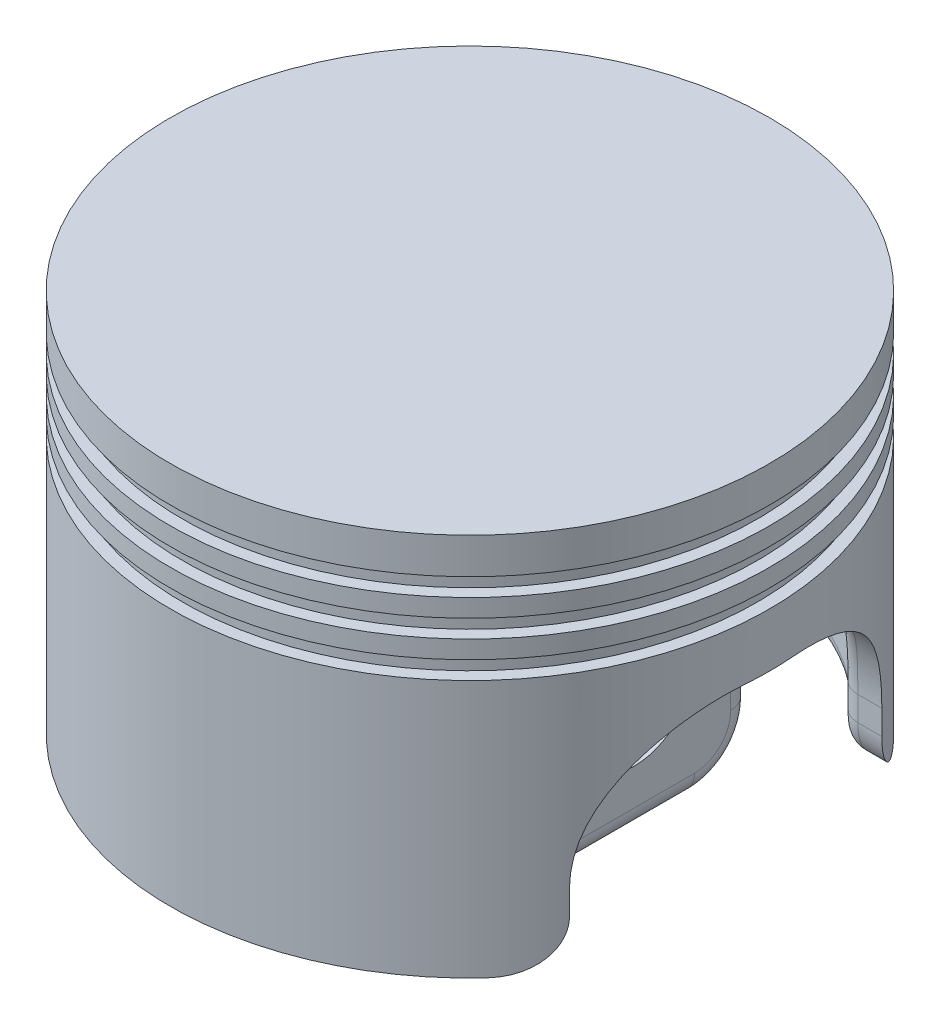
SolidWorks part; units mm, degrees
ref_plane "Front Plane" through (0, 0, 0) normal (0, 0, 1) x (1, 0, 0)
ref_plane "Top Plane" through (0, 0, 0) normal (0, 1, 0) x (1, 0, 0)
ref_plane "Right Plane" through (0, 0, 0) normal (1, 0, 0) x (0, 0, -1)
sketch "Sketch1" plane through (0, 0, 0) normal (1, 0, 0) x (0, 0, -1)
  line L0 (0, 0) -> (63.5, 0)
  line L1 (63.5, 0) -> (63.5, -81.28)
  line L2 (63.5, -81.28) -> (57.15, -81.28)
  line L3 (57.15, -81.28) -> (57.15, -19)
  line L4 (57.15, -19) -> (0, -19)
  line L5 (0, -19) -> (0, 0)
  dimension "D1" = 63.5
  dimension "D2" = 81.28
  dimension "D3" = 6.35
  dimension "D4" = 19
revolve "Revolve1" add sketch "Sketch1" angle 360 about L5
sketch "Sketch2" plane through (0, 0, 0) normal (0, 0, 1) x (1, 0, 0)
  line L0 (63.5, -7.62) -> (60.96, -7.62)
  line L1 (60.96, -7.62) -> (60.96, -11.43)
  line L2 (60.96, -11.43) -> (63.5, -11.43)
  line L3 (63.5, -11.43) -> (63.5, -7.62)
  line L4 (63.5, 0) -> (-63.5, 0) construction
  dimension "D1" = 7.62
  dimension "D2" = 3.81
  dimension "D3" = 2.54
  dimension "D4" = 63.5
ref_axis "Axis1" through (0, -85.344, 0) along (0, 1, 0)
revolve "Cut-Revolve1" cut sketch "Sketch2" angle 360 about axis through (0, -85.344, 0) along (0, 1, 0)
pattern_linear "LPattern2" count 3 spacing 7.62 along (0, -1, 0) of "Cut-Revolve1"
sketch "Sketch3" plane through (0, 0, 0) normal (1, 0, 0) x (0, 0, -1)
  line L0 (0, -85.344) -> (0, 4.064) construction
  line L1 (-33.1, -38.1) -> (33.1, -38.1)
  line L2 (-33.1, -38.1) -> (-33.1, -81.28)
  line L3 (-33.1, -81.28) -> (33.1, -81.28)
  line L4 (33.1, -38.1) -> (33.1, -81.28)
  line L5 (-33.1, -38.1) -> (33.1, -81.28) construction
  line L6 (-33.1, -81.28) -> (33.1, -38.1) construction
  line L7 (63.5, 0) -> (-63.5, 0) construction
  line L8 (-57.15, -81.28) -> (57.15, -81.28) construction
  point P0 (0, -59.69)
  dimension "D1" = 66.2
  dimension "D2" = 38.1
extrude "Cut-Extrude1" cut sketch "Sketch3" against normal mid plane 171
fillet "Fillet1" radius 28 4 edges at (-50.3898, -38.1, 33.1) (-50.3898, -38.1, -33.1) (50.3898, -38.1, -33.1) (50.3898, -38.1, 33.1)
sketch "Sketch4" plane through (0, -19, 0) normal (0, -1, 0) x (1, 0, 0)
  line L1 (-34.875, 25.4) -> (-15.875, 25.4)
  line L2 (-34.875, 25.4) -> (-34.875, -25.4)
  line L3 (-34.875, -25.4) -> (-15.875, -25.4)
  line L4 (-15.875, 25.4) -> (-15.875, -25.4)
  line L5 (-34.875, 25.4) -> (-15.875, -25.4) construction
  line L6 (-34.875, -25.4) -> (-15.875, 25.4) construction
  point P0 (-25.375, 0)
  dimension "D1" = 15.875
  dimension "D2" = 19
  dimension "D3" = 50.8
extrude "Boss-Extrude1" add sketch "Sketch4" along normal blind 63.5
mirror "Mirror1" about plane through (0, 0, 0) normal (1, 0, 0) of "Boss-Extrude1"
sketch "Sketch5" plane through (-34.875, 0, 0) normal (-1, 0, 0) x (0, 0, 1)
  line L0 (0, -85.344) -> (0, 4.064) construction
  line L1 (25.4, -82.5) -> (-25.4, -82.5) construction
  circle A0 centre (0, -57.1) radius 12.7
  dimension "D2" = 25.4
  dimension "D1" = 25.4
extrude "Cut-Extrude2" cut sketch "Sketch5" against normal blind 136.5
fillet "Fillet2" radius 12.7 4 edges at (25.375, -82.5, 25.4) (25.375, -82.5, -25.4) (-25.375, -82.5, 25.4) (-25.375, -82.5, -25.4)
fillet "Fillet3" radius 10 4 edges at (-50.3898, -81.28, 33.1) (50.3898, -81.28, 33.1) (50.3898, -81.28, -33.1) (-50.3898, -81.28, -33.1)
fillet "Fillet4" radius 5 20 edges at (15.875, -44.4, -25.4) (15.875, -78.7803, -21.6803) (15.875, -44.4, 25.4) (15.875, -78.7803, 21.6803) (34.875, -44.4, 25.4) (34.875, -78.7803, 21.6803) (34.875, -44.4, -25.4) (34.875, -78.7803, -21.6803) (-34.875, -44.4, 25.4) (-34.875, -78.7803, 21.6803) (-34.875, -44.4, -25.4) (-34.875, -78.7803, -21.6803) (-15.875, -44.4, -25.4) (-15.875, -78.7803, -21.6803) (-15.875, -44.4, 25.4) (-15.875, -78.7803, 21.6803) (15.875, -82.5, 0) (34.875, -82.5, 0) (-34.875, -82.5, 0) (-15.875, -82.5, 0)
fillet "Fillet5" radius 5 16 edges at (45.4619, -76.5982, 34.6314) (46.5888, -68.69, 33.1) (52.8853, -43.5238, 21.6625) (57.15, -38.1, 0) (49.6267, -50.4868, -28.3428) (46.5888, -68.69, -33.1) (44.2721, -78.4605, -36.1401) (0, -81.28, -57.15) (-45.4619, -76.5982, -34.6314) (-46.5888, -68.69, -33.1) (-52.8853, -43.5238, -21.6625) (-57.15, -38.1, 0) (-49.6267, -50.4868, 28.3428) (-46.5888, -68.69, 33.1) (-44.2721, -78.4605, 36.1401) (0, -81.28, 57.15)
